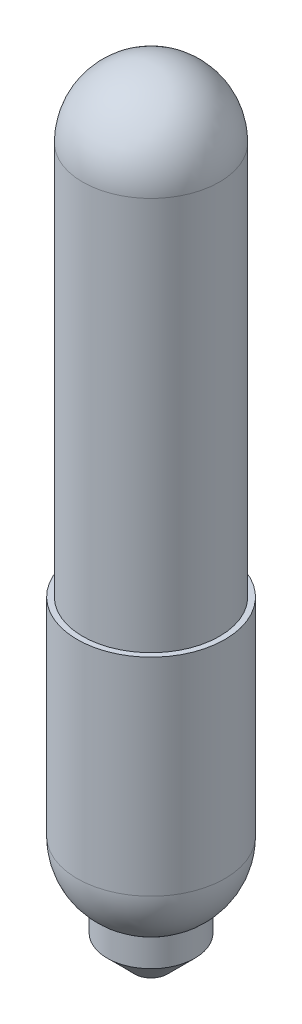
SolidWorks part; units mm, degrees
material "AISI 316 Annealed Stainless Steel Bar (SS)"
ref_plane "Front Plane" through (0, 0, 0) normal (0, 0, 1) x (1, 0, 0)
ref_plane "Top Plane" through (0, 0, 0) normal (0, 1, 0) x (1, 0, 0)
ref_plane "Right Plane" through (0, 0, 0) normal (1, 0, 0) x (0, 0, -1)
sketch "Sketch1" plane through (0, 0, 0) normal (0, 0, 1) x (1, 0, 0)
  line L0 (0, 0) -> (1.016, 0)
  line L1 (1.016, 0) -> (1.016, 1.27)
  line L2 (1.016, 1.27) -> (1.7145, 1.27)
  line L3 (1.7145, 1.27) -> (1.7145, 7.3914)
  line L4 (1.7145, 7.3914) -> (1.5875, 7.3914)
  line L5 (1.5875, 7.3914) -> (1.5875, 18.1102)
  line L6 (1.5875, 18.1102) -> (0, 18.1102)
  line L7 (0, 18.1102) -> (0, 0.444) construction
  line L8 (0, 0) -> (0, 18.1102) construction
  line L9 (0, 0) -> (0, 18.1102)
  dimension "D1" = 6.1214
  dimension "D2" = 3.429
  dimension "D3" = 18.1102
  dimension "D4" = 1.27
  dimension "D5" = 2.032
  dimension "D6" = 3.175
revolve "Revolve1" add sketch "Sketch1" angle 360 about L9
fillet "Fillet1" radius 1.5875 2 edges at (1.5875, 18.1102, 0) (1.7145, 1.27, 0)
chamfer "Chamfer1" distance 0.635 angle 45 1 edges at (1.016, 0, 0)
